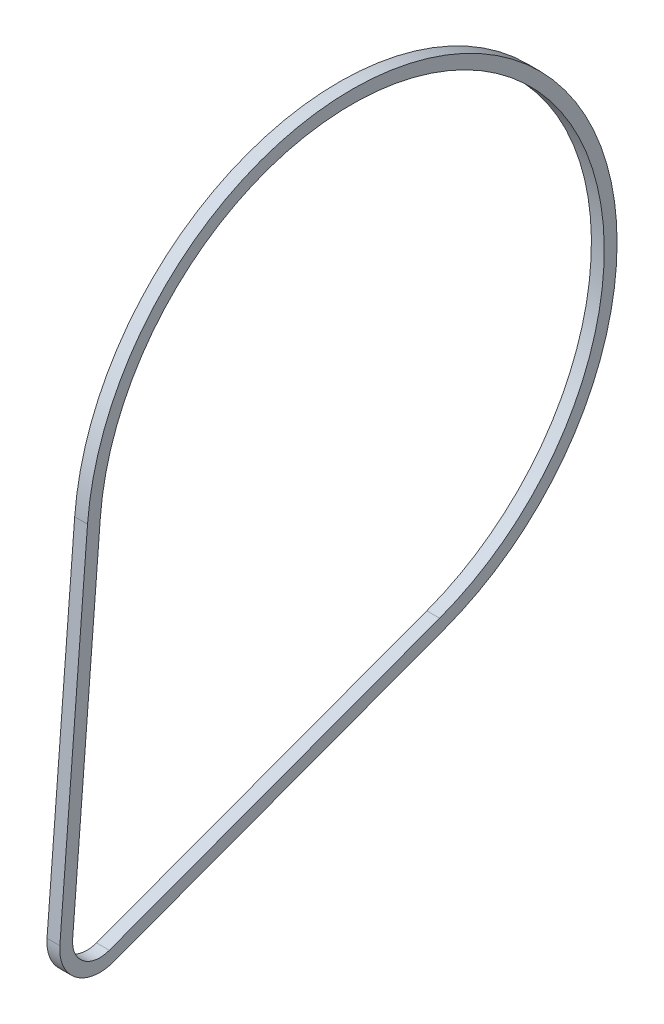
SolidWorks part; units mm, degrees
material "Plain Carbon Steel"
ref_plane "Front Plane" through (0, 0, 0) normal (0, 0, 1) x (1, 0, 0)
ref_plane "Top Plane" through (0, 0, 0) normal (0, 1, 0) x (1, 0, 0)
ref_plane "Right Plane" through (0, 0, 0) normal (1, 0, 0) x (0, 0, -1)
sketch "Sketch1" plane through (0, 0, 0) normal (1, 0, 0) x (0, 0, -1)
  line L0 (113.8529, 148.0498) -> (102.8931, 9.0027)
  line L1 (124.2363, -7.1301) -> (255.0201, 41.3445)
  line L2 (118.9171, 147.6506) -> (107.9574, 8.6035)
  line L3 (122.4708, -2.3668) -> (253.2546, 46.1078)
  arc A0 (107.9574, 8.6035) -> (122.4708, -2.3668) centre (118.7191, 7.7553) ccw
  arc A1 (102.8931, 9.0027) -> (124.2363, -7.1301) centre (118.7191, 7.7553) ccw
  arc A2 (253.2546, 46.1078) -> (118.9171, 147.6506) centre (218.5282, 139.7992) ccw
  arc A3 (255.0201, 41.3445) -> (113.8529, 148.0498) centre (218.5282, 139.7992) ccw
  arc A4 (218.8706, 34.7998) -> (222.0321, 34.8577) centre (218.5282, 139.7992) ccw construction
  arc A6 (106.5922, 9.658) -> (107.7619, 13.2888) centre (106.5099, 11.6883) ccw construction
  dimension "D1" = 5.08
  dimension "D2" = 5.08
extrude "Boss-Extrude1" add sketch "Sketch1" along normal blind 5.08
